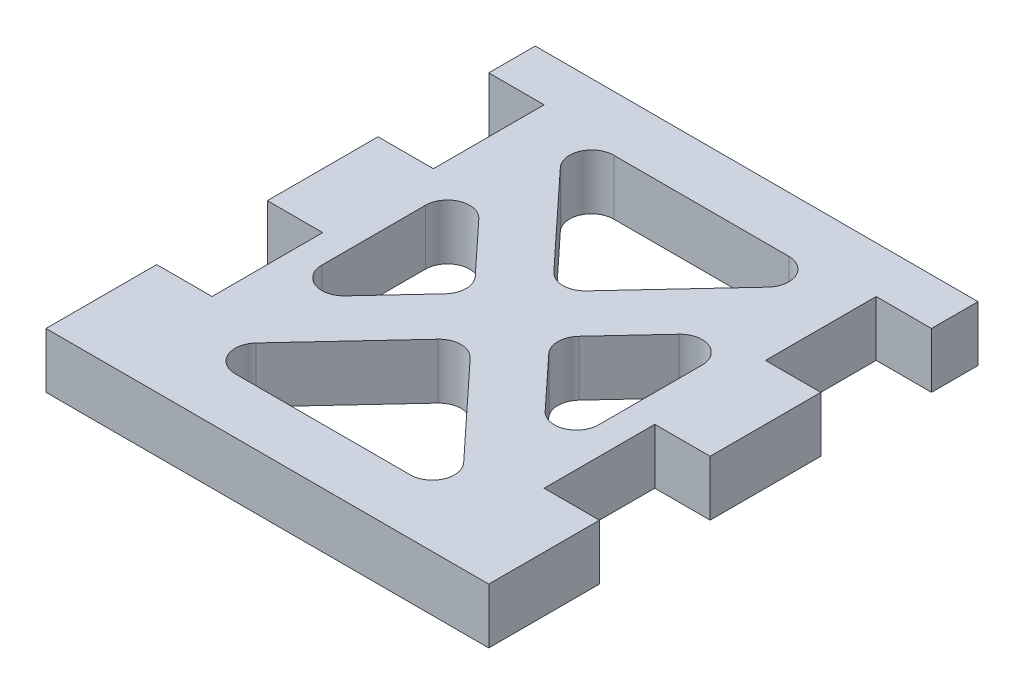
SolidWorks part; units mm, degrees
material "Custom Plastic"
ref_plane "Front Plane" through (0, 0, 0) normal (0, 0, 1) x (1, 0, 0)
ref_plane "Top Plane" through (0, 0, 0) normal (0, 1, 0) x (1, 0, 0)
ref_plane "Right Plane" through (0, 0, 0) normal (1, 0, 0) x (0, 0, -1)
sketch "Sketch1" plane through (0, 0, 0) normal (0, 1, 0) x (1, 0, 0)
  line L1 (25.4, -28.067) -> (-25.4, -28.067)
  line L2 (25.4, -28.067) -> (25.4, 28.067)
  line L3 (25.4, 28.067) -> (-25.4, 28.067)
  line L4 (-25.4, -28.067) -> (-25.4, 28.067)
  line L5 (25.4, -28.067) -> (-25.4, 28.067) construction
  line L6 (25.4, 28.067) -> (-25.4, -28.067) construction
  point P0 (0, 0)
  dimension "D1" = 56.134
  dimension "D2" = 50.8
extrude "Main" add sketch "Sketch1" along normal blind 6.35
sketch "Sketch2" plane through (0, 6.35, 0) normal (0, 1, 0) x (1, 0, 0)
  line L1 (-25.4, 28.067) -> (-25.4, -28.067) construction
  line L2 (-25.4, -15.367) -> (-19.05, -15.367)
  line L3 (-25.4, -15.367) -> (-25.4, -2.667)
  line L4 (-25.4, -2.667) -> (-19.05, -2.667)
  line L5 (-19.05, -15.367) -> (-19.05, -2.667)
  line L6 (-19.05, 10.033) -> (-19.05, -2.667) construction
  line L7 (-25.4, 10.033) -> (-19.05, 10.033)
  line L8 (-25.4, 10.033) -> (-25.4, 22.733)
  line L9 (-25.4, 22.733) -> (-19.05, 22.733)
  line L10 (-19.05, 10.033) -> (-19.05, 22.733)
  line L11 (-19.05, -15.367) -> (-19.05, -28.067) construction
  line L12 (-25.4, -28.067) -> (25.4, -28.067) construction
  line L13 (0, 28.067) -> (0, -28.067) construction
  line L14 (25.4, 28.067) -> (-25.4, 28.067) construction
  line L16 (19.05, -15.367) -> (19.05, -28.067) construction
  line L18 (19.05, 10.033) -> (19.05, -2.667) construction
  line L19 (19.05, 10.033) -> (19.05, 22.733)
  line L20 (25.4, 22.733) -> (19.05, 22.733)
  line L21 (25.4, 10.033) -> (25.4, 22.733)
  line L22 (25.4, 10.033) -> (19.05, 10.033)
  line L23 (19.05, -15.367) -> (19.05, -2.667)
  line L24 (25.4, -2.667) -> (19.05, -2.667)
  line L25 (25.4, -15.367) -> (25.4, -2.667)
  line L26 (25.4, -15.367) -> (19.05, -15.367)
  dimension "D1" = 6.35
  dimension "D2" = 12.7
extrude "Acrylic Mounts" cut sketch "Sketch2" against normal through all
sketch "Sketch3" plane through (0, 6.35, 0) normal (0, 1, 0) x (1, 0, 0)
  line L0 (-15.875, 21.717) -> (0, 4.6603)
  line L1 (0, 4.6603) -> (15.875, 21.717)
  line L2 (15.875, 21.717) -> (-15.875, 21.717)
  line L3 (-15.875, 12.3965) -> (-4.3374, 0)
  line L4 (-4.3374, 0) -> (-15.875, -12.3965)
  line L5 (-15.875, -12.3965) -> (-15.875, 12.3965)
  line L6 (-15.875, -21.717) -> (0, -4.6603)
  line L7 (0, -4.6603) -> (15.875, -21.717)
  line L8 (15.875, -21.717) -> (-15.875, -21.717)
  line L9 (15.875, -12.3965) -> (4.3374, 0)
  line L10 (4.3374, 0) -> (15.875, 12.3965)
  line L11 (15.875, 12.3965) -> (15.875, -12.3965)
  line L16 (25.4, 28.067) -> (-25.4, 28.067) construction
  line L17 (-25.4, -28.067) -> (25.4, -28.067) construction
  line L18 (-19.05, -15.367) -> (-19.05, -2.667) construction
  line L19 (19.05, -2.667) -> (19.05, -15.367) construction
  dimension "D1" = 6.35
  dimension "D2" = 6.35
  dimension "D3" = 3.175
  dimension "D4" = 3.175
  dimension "D5" = 6.35
extrude "Cut-Extrude2" cut sketch "Sketch3" against normal through all
fillet "Fillet1" radius 2.54 12 edges at (15.875, 3.175, 21.717) (15.875, 3.175, 12.3965) (-15.875, 3.175, 21.717) (-15.875, 3.175, 12.3965) (0, 3.175, -4.6603) (-15.875, 3.175, -12.3965) (0, 3.175, 4.6603) (-4.3374, 3.175, 0) (15.875, 3.175, -12.3965) (15.875, 3.175, -21.717) (4.3374, 3.175, 0) (-15.875, 3.175, -21.717)
